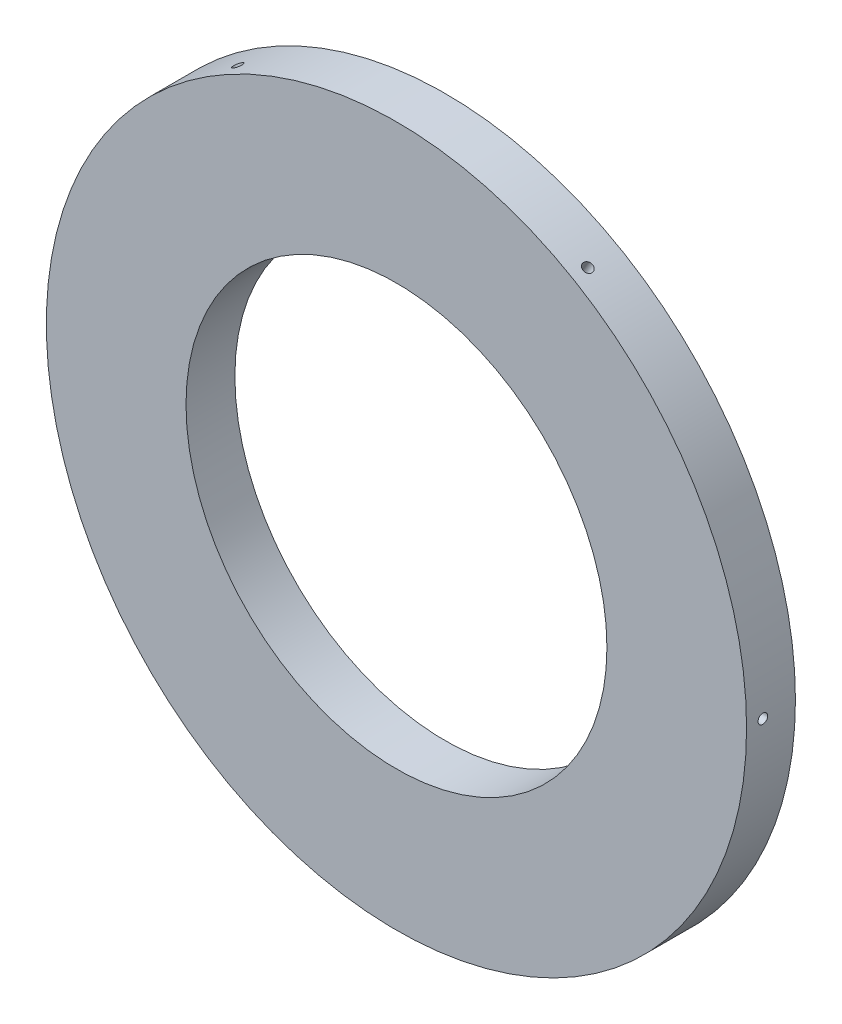
SolidWorks part; units mm, degrees
material "6061-T6 (SS)"
ref_plane "Front" through (0, 0, 0) normal (0, 0, 1) x (1, 0, 0)
ref_plane "Top" through (0, 0, 0) normal (0, 1, 0) x (1, 0, 0)
ref_plane "Right" through (0, 0, 0) normal (1, 0, 0) x (0, 0, -1)
sketch "Sketch1" plane through (0, 0, 0) normal (0, 0, 1) x (1, 0, 0)
  circle A0 centre (0, 0) radius 81.8896
  circle A1 centre (0, 0) radius 49.2252
  dimension "D1" = 163.7792
  dimension "D2" = 98.4504
extrude "Boss-Extrude1" add sketch "Sketch1" along normal blind 11.43
hole_wizard "#4-40 Tapped Hole1" positions "3DSketch1" profile "Sketch2" tap size "#4-40" standard "ANSI Inch"
sketch3d "3DSketch1"
  point P0 (81.8896, 0, 7.62)
  dimension "D1" = 3.81
sketch "Sketch2" plane through (81.8896, 0, 7.62) normal (0, 1, 0) x (0, 0, -1)
  line L0 (0, 0) -> (0, 8.2738)
  line L1 (0, 8.2738) -> (1.1303, 7.5946)
  line L2 (1.1303, 7.5946) -> (1.1303, 0)
  line L5 (1.1303, 0) -> (0, 0)
  line L10 (0, 8.2738) -> (-1.1303, 7.5946) construction
  line L11 (0, -6.35) -> (0, 107.95) construction
  dimension "Tap Drill Dia." = 2.2606
  dimension "Tap Drill Depth" = 7.5946
  dimension "Drill Angle" = 118
cosmetic thread "Hole Thread1" parameters "D1"=5.6896, "D2"=2.8448
pattern_circular "CirPattern1" count 6 over 360 about axis through (0, 0, 11.43) along (0, 0, -1) of "#4-40 Tapped Hole1"
sketch "Sketch3" plane through (0, 0, 0) normal (0, 0, 1) x (1, 0, 0)
  line L0 (0, 0) -> (81.8896, 0) construction
  line L1 (50.927, 0) -> (81.1276, 0) construction
  line L2 (50.8544, -2.7178) -> (81.0821, -2.7178)
  line L3 (0, 0) -> (40.9448, 70.9185) construction
  line L4 (50.8544, 2.7178) -> (81.0821, 2.7178)
  line L5 (50.927, 2.7178) -> (81.1276, 2.7178) construction
  line L6 (50.927, -2.7178) -> (81.1276, -2.7178) construction
  line L7 (25.4635, 44.1041) -> (40.9448, 70.9185)
  line L8 (27.7809, 42.6823) -> (43.2985, 69.5596)
  line L9 (23.0735, 45.4001) -> (38.5911, 72.2774)
  line L10 (27.8172, 42.7452) -> (43.2985, 69.5596) construction
  line L11 (23.1098, 45.463) -> (38.5911, 72.2774) construction
  circle A0 centre (0, 0) radius 81.8896 construction
  circle A1 centre (0, 0) radius 81.1276
  circle A2 centre (0, 0) radius 50.927
  circle A3 centre (0, 0) radius 81.8896
  arc A4 (41.9198, 70.3466) -> (39.962, 71.4769) centre (0, 0) ccw construction
  arc A5 (41.9198, 70.3466) -> (39.962, 71.4769) centre (0, 0) ccw
  arc A6 (81.8818, -1.1303) -> (81.8818, 1.1303) centre (0, 0) ccw construction
  arc A7 (81.8818, -1.1303) -> (81.8818, 1.1303) centre (0, 0) ccw
  point P45 (0, 0)
  dimension "D1" = 0.762
  dimension "D2" = 60
  dimension "D5" = 2.7178
  dimension "D6" = 101.854
  dimension "D3" = 2.7178
  dimension "D4" = 2.7178
  dimension "D7" = 2.7178
extrude "Cut-Extrude1" cut sketch "Sketch3" along normal blind 10.922 contours L4 A2 L8 A1
fillet "Fillet2" radius 4.9276 2 edges at (42.8947, 68.8602, 5.461) (81.0821, 2.7178, 5.461)
fillet "Fillet4" radius 6.35 2 edges at (27.7809, 42.6823, 5.461) (50.8544, 2.7178, 5.461) tangent propagation no
fillet "Fillet3" radius 1.5875 8 edges at (79.4704, 4.3405, 10.922) (66.1851, 2.7178, 10.922) (44.1041, 25.4635, 10.922) (35.4462, 55.9591, 10.922) (43.4942, 66.6532, 10.922) (70.2586, 40.5638, 10.922) (52.4353, 4.2353, 10.922) (29.8855, 43.2926, 10.922)
pattern_circular "CirPattern2" count 6 over 360 about axis through (0, 0, 11.43) along (0, 0, -1) of "Cut-Extrude1", "Fillet2", "Fillet3", "Fillet4"
sketch "Sketch4" plane through (0, 0, 0) normal (0, 0, -1) x (-1, 0, 0)
  line L0 (-81.8896, 0) -> (0, 0) construction
  line L1 (0, 0) -> (0, -81.8896) construction
  line L2 (0, -81.8896) -> (-81.8896, -81.8896) construction
  line L3 (-81.8896, -81.8896) -> (-81.8896, 0) construction
  dimension "D1" = 81.8896
  dimension "D2" = 81.8896
ref_plane "Plane1" through (0, 0, 0) normal (0.866, -0.5, 0) x (0, 0, -1)
ref_plane "Plane2" through (0, 0, 0) normal (0.866, 0.5, 0) x (0, 0, -1)
